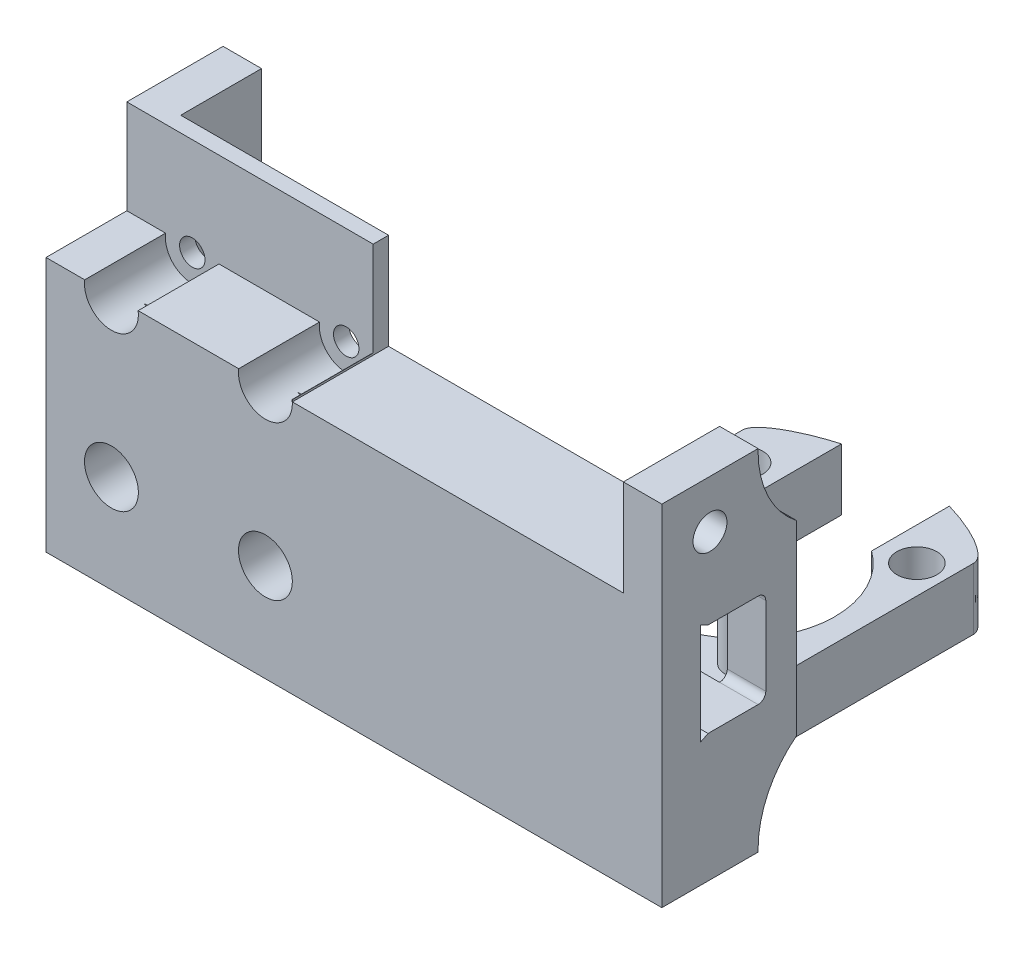
SolidWorks part; units mm, degrees
ref_plane "Front Plane" through (0, 0, 0) normal (0, 0, 1) x (1, 0, 0)
ref_plane "Top Plane" through (0, 0, 0) normal (0, 1, 0) x (1, 0, 0)
ref_plane "Right Plane" through (0, 0, 0) normal (1, 0, 0) x (0, 0, -1)
sketch "Sketch1" plane through (0, 0, 0) normal (0, 0, 1) x (1, 0, 0)
  line L1 (0, 0) -> (80, 0)
  line L2 (0, 0) -> (0, 45.4)
  line L3 (0, 45.4) -> (80, 45.4)
  line L4 (80, 0) -> (80, 45.4)
  line L5 (8.5, 32.7) -> (28.5, 32.7) construction
  line L6 (8.5, 32.7) -> (8.5, 12.7) construction
  line L7 (8.5, 12.7) -> (28.5, 12.7) construction
  line L8 (28.5, 32.7) -> (28.5, 12.7) construction
  circle A0 centre (8.5, 32.7) radius 1.65
  circle A1 centre (28.5, 32.7) radius 1.65
  circle A2 centre (28.5, 12.7) radius 1.65
  circle A3 centre (8.5, 12.7) radius 1.65
  dimension "D3" = 3.3
  dimension "D1" = 45.4
  dimension "D2" = 80
  dimension "D4" = 12.7
  dimension "D5" = 20
  dimension "D6" = 8.5
extrude "Boss-Extrude1" add sketch "Sketch1" along normal blind 12.5
sketch "Sketch2" plane through (0, 0, 0) normal (0, 0, -1) x (-1, 0, 0)
  line L0 (0, 0) -> (-80, 0) construction
  line L1 (0, 45.4) -> (-5, 45.4)
  line L2 (0, 45.4) -> (0, 0)
  line L3 (0, 0) -> (-5, 0)
  line L4 (-5, 45.4) -> (-5, 0)
  dimension "D1" = 5
extrude "Boss-Extrude2" add sketch "Sketch2" along normal blind 10.5
sketch "Sketch3" plane through (0, 0, 0) normal (0, 0, 1) x (1, 0, 0)
  line L0 (80, 0) -> (80, 45.4) construction
  line L1 (80, 28.8) -> (0, 28.8)
  line L2 (80, 28.8) -> (80, 16.6)
  line L3 (80, 16.6) -> (0, 16.6)
  line L4 (0, 28.8) -> (0, 16.6)
  line L5 (0, 0) -> (0, 45.4) construction
  line L6 (80, 22.7) -> (0, 22.7) construction
  point P10 (80, 22.7)
  dimension "D1" = 12.2
extrude "Cut-Extrude1" cut sketch "Sketch3" against normal through all and the other way blind 7.5
sketch "Sketch4" plane through (0, 0, 0) normal (0, 0, -1) x (-1, 0, 0)
  line L1 (-69.5, 0) -> (-39.5, 0)
  line L2 (-69.5, 0) -> (-69.5, 8)
  line L3 (-69.5, 8) -> (-39.5, 8)
  line L4 (-39.5, 0) -> (-39.5, 8)
  line L7 (-5, 0) -> (-80, 0) construction
  dimension "D1" = 8
  dimension "D2" = 30
  dimension "D3" = 39.5
extrude "Boss-Extrude3" add sketch "Sketch4" along normal blind 44.5
sketch "Sketch5" plane through (0, 8, 0) normal (0, 1, 0) x (1, 0, 0)
  line L0 (69.5, 44.5) -> (69.5, 0) construction
  line L1 (80, 0) -> (5, 0) construction
  circle A0 centre (54.4956, 23.5) radius 12
  dimension "D1" = 24
  dimension "D2" = 15.0044
  dimension "D3" = 23.5
extrude "Cut-Extrude2" cut sketch "Sketch5" against normal blind 45
sketch "Sketch6" plane through (0, 16.6, 0) normal (0, -1, 0) x (1, 0, 0)
  circle A3 centre (54.4956, -39.5013) radius 2.6
  circle A4 centre (65.8093, -34.815) radius 2.6
  circle A5 centre (43.1819, -34.815) radius 2.6
  dimension "D1" = 5.2
extrude "Cut-Extrude3" cut sketch "Sketch6" against normal through all both and the other way through all
fillet "Fillet1" radius 6 2 edges at (39.5, 4, -44.5) (69.5, 4, -44.5) second distance 15 conic rho 0.3 first distance on face at (39.5, 4, -22.25) first distance on face at (69.5, 4, -22.25)
sketch "Sketch8" plane through (0, 0, 12.5) normal (0, 0, 1) x (1, 0, 0)
  circle A0 centre (8.5, 32.7) radius 3.5
  circle A1 centre (28.5, 32.7) radius 3.5
  circle A2 centre (8.5, 12.7) radius 3.5
  circle A3 centre (28.5, 12.7) radius 3.5
  dimension "D1" = 7
extrude "Cut-Extrude5" cut sketch "Sketch8" against normal offset from surface (10.5 mm away) 2 up to face at (10.15, 12.7, 0)
sketch "Sketch12" plane through (0, 0, 12.5) normal (0, 0, 1) x (1, 0, 0)
  line L0 (80, 45.4) -> (0, 45.4) construction
  line L5 (0, 45.4) -> (45, 45.4)
  line L6 (0, 45.4) -> (0, 33.15)
  line L7 (0, 33.15) -> (45, 33.15)
  line L8 (45, 45.4) -> (45, 33.15)
  line L9 (0, 45.4) -> (0, 0) construction
  dimension "D1" = 12.25
  dimension "D2" = 45
extrude "Cut-Extrude8" cut sketch "Sketch12" against normal offset from surface (10.5 mm away) 2 up to face at (10.15, 32.7, 0)
sketch "Sketch13" plane through (0, 8, 0) normal (0, 1, 0) x (1, 0, 0)
  line L1 (61.4956, 51.1384) -> (47.4956, 51.1384)
  line L2 (61.4956, 51.1384) -> (61.4956, 27.8643)
  line L3 (61.4956, 27.8643) -> (47.4956, 27.8643)
  line L4 (47.4956, 51.1384) -> (47.4956, 27.8643)
  line L5 (61.4956, 51.1384) -> (47.4956, 27.8643) construction
  line L6 (61.4956, 27.8643) -> (47.4956, 51.1384) construction
  point P0 (54.4956, 39.5013)
  dimension "D1" = 14
extrude "Cut-Extrude10" cut sketch "Sketch13" against normal blind 10
sketch "Sketch14" plane through (0, 0, 0) normal (0, 0, -1) x (-1, 0, 0)
  line L1 (-80, 28.8) -> (0, 28.8)
  line L2 (-80, 28.8) -> (-80, 16.6)
  line L3 (-80, 16.6) -> (0, 16.6)
  line L4 (0, 28.8) -> (0, 16.6)
extrude "Boss-Extrude5" [suppressed] add sketch "Sketch14" against normal blind 0.5
sketch "Sketch15" plane through (0, 8, 0) normal (0, 1, 0) x (1, 0, 0)
  circle A0 centre (54.4956, 7.5013) radius 2.3
  circle A1 centre (65.8093, 12.1876) radius 2.3
  circle A2 centre (43.1819, 12.1876) radius 2.3
  dimension "D1" = 4.6
extrude "Boss-Extrude6" add sketch "Sketch15" along normal blind 8
sketch "Sketch16" plane through (0, 45.4, 0) normal (0, 1, 0) x (1, 0, 0)
  line L0 (39.5, 0) -> (69.5, 0) construction
  line L1 (75, 0) -> (32, 0)
  line L2 (75, 0) -> (75, -12.5)
  line L3 (75, -12.5) -> (32, -12.5)
  line L4 (32, 0) -> (32, -12.5)
  line L5 (80, -12.5) -> (45, -12.5) construction
  line L6 (80, -12.5) -> (80, 0) construction
  dimension "D1" = 32
  dimension "D2" = 5
extrude "Cut-Extrude11" cut sketch "Sketch16" against normal blind 12.5
sketch "Sketch17" plane through (80, 0, 0) normal (1, 0, 0) x (0, 0, -1)
  line L0 (-12.5, 45.4) -> (0, 45.4) construction
  line L1 (-6.25, 45.4) -> (-6.25, 28.8) construction
  line L2 (-7.5, 28.8) -> (0, 28.8) construction
  circle A0 centre (-6.25, 39.15) radius 2.2
  dimension "D1" = 4.4
  dimension "D2" = 6.25
extrude "Cut-Extrude12" cut sketch "Sketch17" against normal blind 10
sketch "Sketch18" plane through (80, 0, 0) normal (1, 0, 0) x (0, 0, -1)
  line L0 (-7.5, 28.8) -> (-6.5, 28.8)
  line L1 (-7.5, 28.8) -> (0, 28.8) construction
  line L2 (-6.5, 28.8) -> (-7.5, 29.3)
  line L3 (-7.5, 29.3) -> (-7.5, 28.8)
  line L4 (-7.5, 16.6) -> (-7.5, 16.1)
  line L5 (-7.5, 16.1) -> (-6.5, 16.6)
  line L6 (-7.5, 16.6) -> (0, 16.6) construction
  line L7 (-6.5, 16.6) -> (-7.5, 16.6)
  dimension "D1" = 0.5
  dimension "D2" = 1
  dimension "D3" = 1
  dimension "D4" = 0.5
extrude "Cut-Extrude13" cut sketch "Sketch18" against normal through all
sketch "Sketch19" plane through (0, 0, 0) normal (0, 0, -1) x (-1, 0, 0)
  line L0 (-80, 0) -> (-80, 16.6) construction
  line L1 (-75, 34.8) -> (-80, 34.8)
  line L2 (-75, 34.8) -> (-75, 10.6)
  line L3 (-75, 10.6) -> (-80, 10.6)
  line L4 (-80, 34.8) -> (-80, 10.6)
  line L5 (-5, 16.6) -> (-80, 16.6) construction
  line L6 (-80, 28.8) -> (-5, 28.8) construction
  line L7 (-75, 32.9) -> (-75, 45.4) construction
  dimension "D1" = 6
  dimension "D2" = 6
extrude "Boss-Extrude7" add sketch "Sketch19" along normal blind 5
sketch "Sketch20" plane through (80, 0, 0) normal (1, 0, 0) x (0, 0, -1)
  line L0 (0, 28.8) -> (0, 16.6)
  line L1 (0, 28.8) -> (1, 28.8)
  line L2 (0, 16.6) -> (1, 16.6)
  line L3 (1, 28.8) -> (1, 16.6)
  dimension "D1" = 1
extrude "Cut-Extrude14" cut sketch "Sketch20" against normal through all
sketch "Sketch21" plane through (0, 16.6, 0) normal (0, 1, 0) x (1, 0, 0)
  line L0 (5, 0) -> (5, 10.5) construction
  line L1 (0, 10.5) -> (5, 10.5)
  line L2 (0, 10.5) -> (0, 1)
  line L3 (0, 1) -> (5, 1)
  line L4 (5, 10.5) -> (5, 1)
  dimension "D1" = 9.5
extrude "Boss-Extrude8" add sketch "Sketch21" along normal up to surface (12.2 mm away) up to face at (40, 28.8, -1.25)
fillet "Fillet2" radius 1 4 edges at (77.5, 16.6, -1) (77.5, 28.8, -1) (2.5, 16.6, -1) (2.5, 28.8, -1)
fillet "Fillet3" radius 13 2 edges at (77.5, 10.6, 0) (77.5, 34.8, 0)
